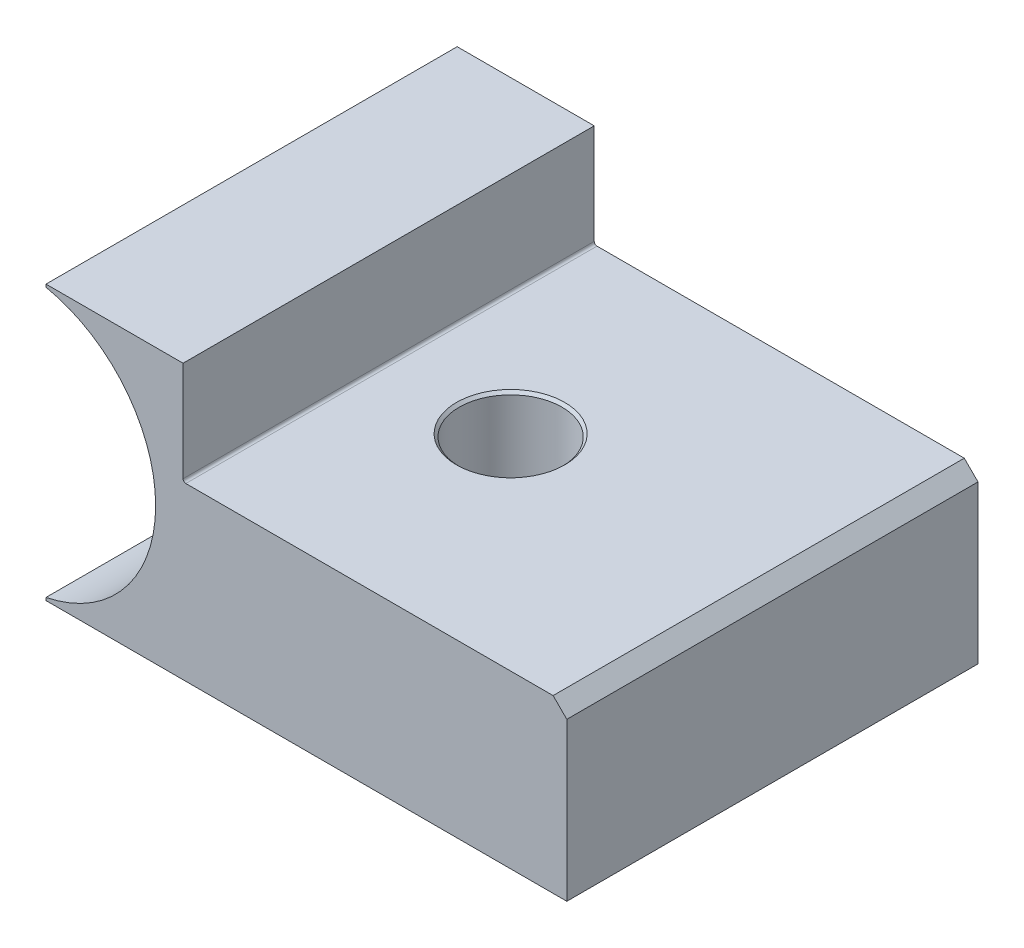
SolidWorks part; units mm, degrees
material "AISI Type A2 Tool Steel Custom"
ref_plane "Front Plane" through (0, 0, 0) normal (0, 0, 1) x (1, 0, 0)
ref_plane "Top Plane" through (0, 0, 0) normal (0, 1, 0) x (1, 0, 0)
ref_plane "Right Plane" through (0, 0, 0) normal (1, 0, 0) x (0, 0, -1)
sketch "Sketch1" plane through (0, 0, 0) normal (0, 0, 1) x (1, 0, 0)
  line L1 (2.54, 0) -> (50.8, 0)
  line L3 (2.54, 25.4) -> (15.24, 25.4)
  line L4 (50.8, 0) -> (50.8, 15.875)
  line L5 (2.54, 25.4) -> (2.54, 25.1434)
  line L6 (15.24, 25.4) -> (15.24, 15.875)
  line L7 (15.24, 15.875) -> (50.8, 15.875)
  line L8 (2.54, 0.2566) -> (2.54, 0)
  arc A1 (2.54, 0.2566) -> (2.54, 25.1434) centre (0, 12.7) ccw
  point P0 (0, 0)
  dimension "D2" = 25.4
  dimension "D1" = 12.7
  dimension "D3" = 9.525
  dimension "D4" = 2.54
  dimension "D5" = 35.56
  dimension "D6" = 15.875
  dimension "D7" = 0.2566
extrude "Boss-Extrude1" add sketch "Sketch1" along normal blind 38.1
sketch "Sketch2" plane through (0, 15.875, 0) normal (0, 1, 0) x (1, 0, 0)
  line L0 (0, -38.1) -> (0, 0) construction
  point P0 (26.543, -19.05)
  point P5 (0, -19.05)
  dimension "D1" = 26.543
hole_wizard "3/8 (0.375) Diameter Hole1" positions "Sketch2" profile "Sketch4" hole size "3/8" standard "ANSI Inch" end condition through all
sketch "Sketch4" plane through (26.543, 15.875, 19.05) normal (1, 0, 0) x (0, 0, 1)
  line L0 (0, 0) -> (0, 15.875)
  line L1 (0, 15.875) -> (4.7625, 15.875)
  line L2 (4.7625, 15.875) -> (4.7625, 0)
  line L5 (4.7625, 0) -> (0, 0)
  line L11 (0, -6.35) -> (0, 107.95) construction
  dimension "Thru Hole Dia." = 9.525
  dimension "Thru Hole Depth" = 15.875
chamfer "Chamfer1" distance 1.27 angle 45 1 edges at (50.8, 15.875, 19.05)
chamfer "Chamfer2" distance 0.254 angle 45 1 edges at (26.543, 15.875, 23.8125)
fillet "Fillet1" radius 0.254 1 edges at (15.24, 15.875, 19.05)
